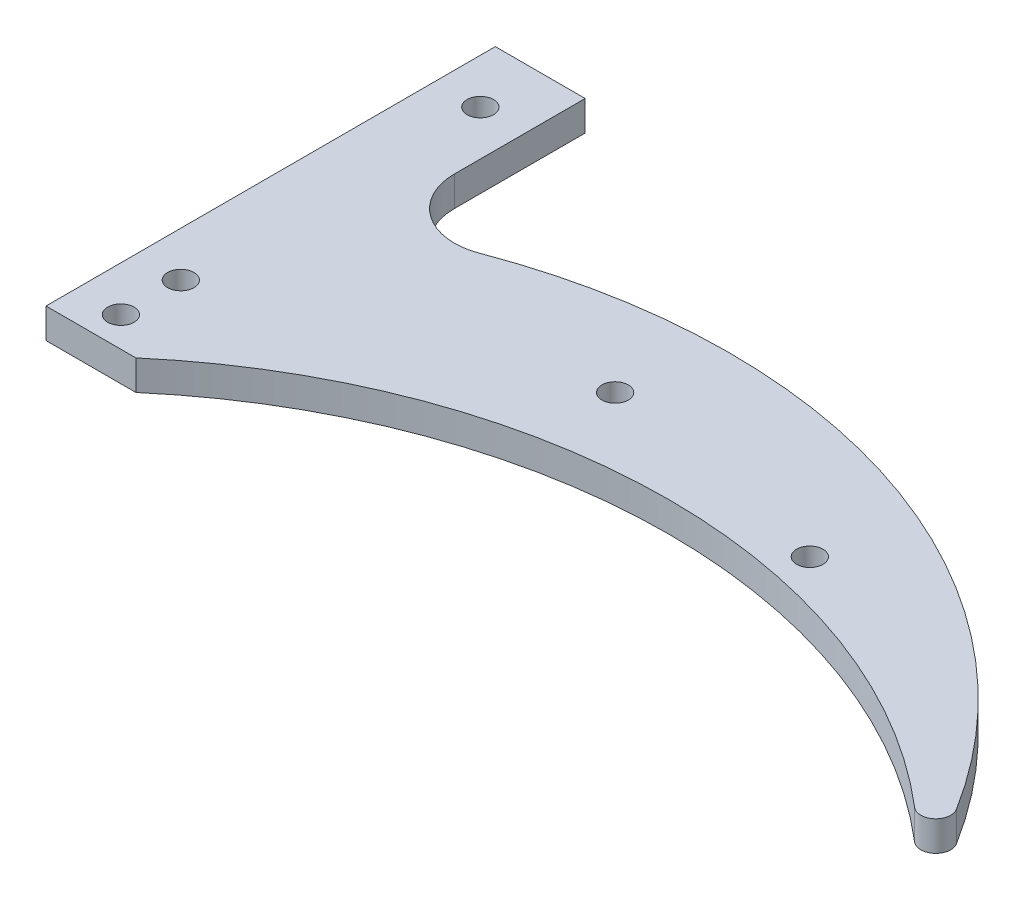
SolidWorks part; units mm, degrees
ref_plane "Front Plane" through (0, 0, 0) normal (0, 0, 1) x (1, 0, 0)
ref_plane "Top Plane" through (0, 0, 0) normal (0, 1, 0) x (1, 0, 0)
ref_plane "Right Plane" through (0, 0, 0) normal (1, 0, 0) x (0, 0, -1)
sketch "Sketch1" plane through (0, 0, 0) normal (0, 1, 0) x (1, 0, 0)
  line L0 (0, 0) -> (130, 0) construction
  line L1 (0, 75) -> (0, 53.1659)
  line L2 (0, 0) -> (-15, 0)
  line L3 (0, 0) -> (0, 75) construction
  line L4 (0, 75) -> (-15, 75)
  line L5 (-15, 0) -> (-15, 75)
  line L6 (-7.5, 0) -> (-7.5, 75) construction
  arc A0 (0, 0) -> (130, 0) centre (65, -75.9934) cw
  arc A1 (13.5374, 43.8125) -> (133.7458, 3.2235) centre (48.9119, -49.7217) cw
  arc A2 (130, 0) -> (133.7458, 3.2235) centre (131.625, 1.8998) ccw
  arc A3 (13.5374, 43.8125) -> (0, 53.1659) centre (10, 53.1659) cw
  circle A4 centre (-7.5, 5) radius 2.2
  circle A5 centre (-7.5, 15) radius 2.2
  circle A6 centre (-7.5, 65) radius 2.2
  circle A7 centre (85, 27.5) radius 2.2
  circle A8 centre (45, 35) radius 2.2
  point P13 (0, 37.5)
  dimension "D2" = 100
  dimension "D3" = 100
  dimension "D5" = 2.5
  dimension "D7" = 10
  dimension "D11" = 4.4
  dimension "D12" = 4.4
  dimension "D13" = 4.4
  dimension "D14" = 4.4
  dimension "D17" = 4.4
  dimension "D18" = 70
  dimension "D19" = 60
  dimension "D1" = 130
  dimension "D4" = 75
  dimension "D6" = 15
  dimension "D8" = 5
  dimension "D9" = 10
  dimension "D10" = 10
  dimension "D15" = 27.5
  dimension "D16" = 100
extrude "Boss-Extrude1" add sketch "Sketch1" along normal blind 5
